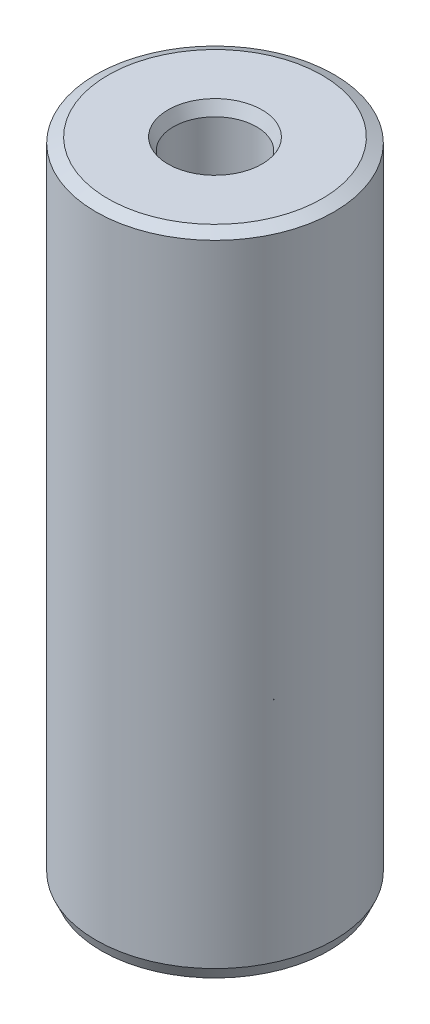
SolidWorks part; units mm, degrees
ref_plane "Front Plane" through (0, 0, 0) normal (0, 0, 1) x (1, 0, 0)
ref_plane "Top Plane" through (0, 0, 0) normal (0, 1, 0) x (1, 0, 0)
ref_plane "Right Plane" through (0, 0, 0) normal (1, 0, 0) x (0, 0, -1)
sketch "Sketch1" plane through (0, 0, 0) normal (0, 1, 0) x (1, 0, 0)
  circle A0 centre (0, 0) radius 5
  dimension "SLEEVE_OD" = 10
extrude "Boss-Extrude1" add sketch "Sketch1" along normal blind 27.2205
sketch "Sketch2" plane through (0, 0, 0) normal (0, 1, 0) x (1, 0, 0)
  circle A0 centre (0, 0) radius 1.7471
  dimension "BORE_D" = 3.4942
extrude "Cut-Extrude1" cut sketch "Sketch2" along normal through all
chamfer "Chamfer1" distance 0.2274 angle 65.679 4 edges at (0, 27.2205, 1.7471) (0, 0, 1.7471) (0, 0, 5) (0, 27.2205, 5) first distance on face at (0, 27.2205, 1.7471) first distance on face at (0, 0, 1.7471) first distance on face at (0, 27.2205, 5)
